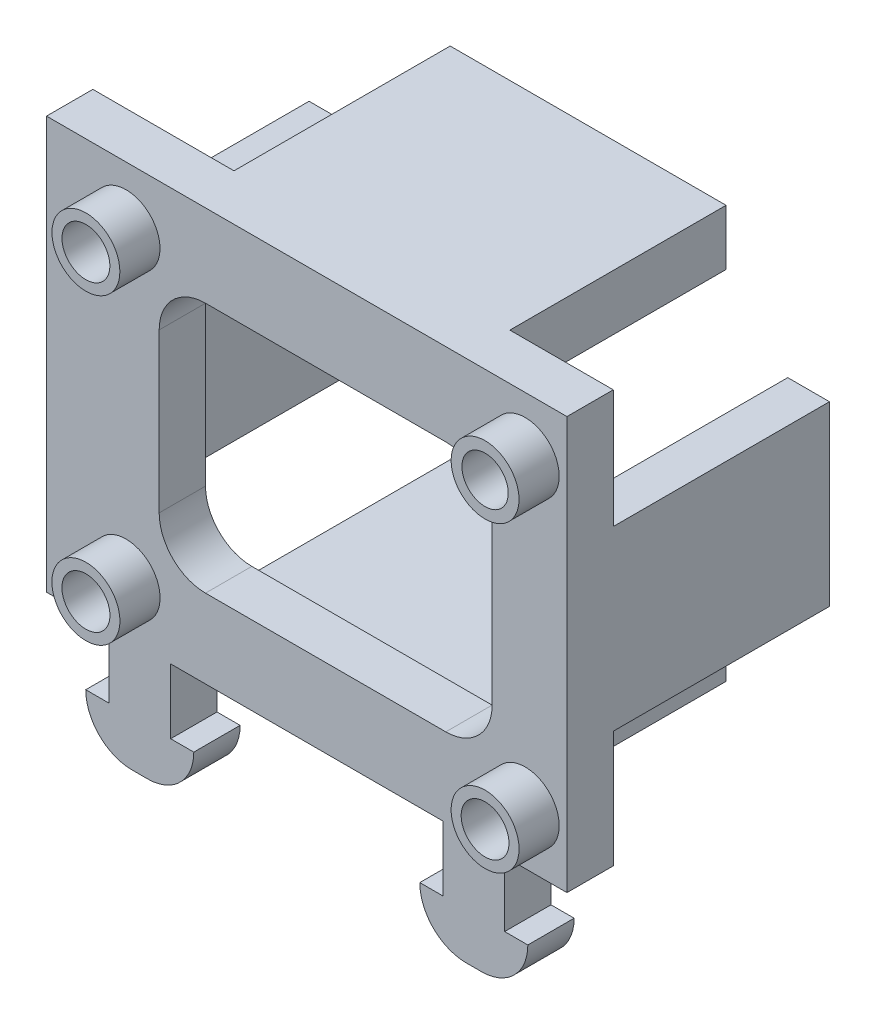
SolidWorks part; units mm, degrees
ref_plane "Спереди" through (0, 0, 0) normal (0, 0, 1) x (1, 0, 0)
ref_plane "Сверху" through (0, 0, 0) normal (0, 1, 0) x (1, 0, 0)
ref_plane "Справа" through (0, 0, 0) normal (1, 0, 0) x (0, 0, -1)
sketch "Эскиз2" plane through (0, 0, 0) normal (0, 0, 1) x (1, 0, 0)
  line L0 (33.7, 0) -> (30.9983, 0) construction
  line L1 (33.7, 26.7) -> (0, 26.7)
  line L2 (33.7, 26.7) -> (33.7, 0)
  line L3 (33.7, 0) -> (0, 0)
  line L4 (0, 26.7) -> (0, 0)
  line L5 (30.9983, 0) -> (30.9983, 3.4986) construction
  line L6 (30.9983, 3.4986) -> (33.7, 3.4986) construction
  line L7 (33.7, 26.7) -> (30.9983, 26.7) construction
  line L8 (30.9983, 26.7) -> (30.9983, 23.0985) construction
  line L9 (30.9983, 23.0985) -> (33.7, 23.0985) construction
  line L10 (0, 0) -> (5.1505, 0) construction
  line L11 (5.1505, 0) -> (5.1505, 3.3527) construction
  line L12 (5.1505, 3.3527) -> (0, 3.3527) construction
  line L13 (0, 26.7) -> (5.1505, 26.7) construction
  line L14 (5.1505, 26.7) -> (5.1505, 22.95) construction
  line L15 (5.1505, 22.95) -> (0, 22.95) construction
  line L16 (5.1505, 22.95) -> (30.9983, 3.4986) construction
  circle A0 centre (30.9983, 3.4986) radius 1.5002
  circle A1 centre (30.9983, 23.0985) radius 1.5
  circle A2 centre (5.1505, 3.3527) radius 1.5523
  circle A3 centre (5.1505, 22.95) radius 1.5465
  point P12 (30.9983, 21.5985)
  point P13 (30.9983, 4.9988)
  point P14 (30.9983, 1.9985)
  point P15 (30.9983, 24.5985)
  point P16 (32.4984, 3.4986)
  point P25 (5.1505, 21.4035)
  point P26 (5.1505, 24.4965)
  dimension "D1" = 26.7
  dimension "D2" = 33.7
extrude "Бобышка-Вытянуть1" add sketch "Эскиз2" along normal blind 2 and the other way blind 1
sketch "Эскиз4" plane through (0, 0, 2) normal (0, 0, 1) x (1, 0, 0)
  line L0 (5.1505, 22.95) -> (30.9983, 3.4986) construction
  line L2 (10.2935, 5.0944) -> (25.8553, 5.0944)
  line L3 (7.2935, 8.0944) -> (7.2935, 18.3542)
  line L4 (10.2935, 21.3542) -> (25.8553, 21.3542)
  line L5 (28.8553, 8.0944) -> (28.8553, 18.3542)
  line L6 (7.2935, 5.0944) -> (28.8553, 21.3542) construction
  line L7 (7.2935, 21.3542) -> (28.8553, 5.0944) construction
  arc A0 (25.8553, 5.0944) -> (28.8553, 8.0944) centre (25.8553, 8.0944) ccw
  arc A1 (10.2935, 5.0944) -> (7.2935, 8.0944) centre (10.2935, 8.0944) cw
  arc A2 (25.8553, 21.3542) -> (28.8553, 18.3542) centre (25.8553, 18.3542) cw
  arc A3 (7.2935, 18.3542) -> (10.2935, 21.3542) centre (10.2935, 18.3542) cw
  point P4 (18.0744, 13.2243)
  dimension "D3" = 3
  dimension "D4" = 3
  dimension "D5" = 3
  dimension "D6" = 3
  dimension "D1" = 16.2598
  dimension "D2" = 21.5618
extrude "Вырез-Вытянуть1" cut sketch "Эскиз4" against normal blind 3
sketch "Эскиз5" plane through (0, 0, 2) normal (0, 0, 1) x (1, 0, 0)
  circle A0 centre (5.1505, 22.95) radius 2.198
  circle A1 centre (30.9983, 23.0985) radius 2.1989
  circle A2 centre (30.9983, 3.4986) radius 2.2003
  circle A3 centre (5.1505, 3.3527) radius 2.2025
  dimension "D1" = 4.396
  dimension "D2" = 4.3978
  dimension "D3" = 4.4006
  dimension "D4" = 4.4049
extrude "Бобышка-Вытянуть2" add sketch "Эскиз5" along normal blind 2.6
sketch "Эскиз6" plane through (0, 0, 4.6) normal (0, 0, 1) x (1, 0, 0)
  circle A0 centre (5.1505, 22.95) radius 1.5512
  circle A1 centre (5.1505, 3.3527) radius 1.5547
  circle A2 centre (30.9983, 3.4986) radius 1.5482
  circle A3 centre (30.9983, 23.0985) radius 1.5
extrude "Вырез-Вытянуть2" cut sketch "Эскиз6" against normal blind 5
sketch "Эскиз10" plane through (0, 0, -1) normal (0, 0, -1) x (-1, 0, 0)
  line L0 (-30.9983, 3.4986) -> (-27.0046, 3.4986) construction
  line L1 (-27.0046, 3.4986) -> (-27.0046, 23.0985) construction
  line L2 (-5.1505, 3.3527) -> (-9.1386, 3.3527) construction
  line L3 (-9.1386, 3.3527) -> (-9.1386, 23.0985) construction
  line L4 (0, 0) -> (-33.7, 0) construction
  line L5 (-27.0046, 3.4986) -> (-9.1386, 3.4986)
  line L6 (-27.0046, 3.4986) -> (-27.0046, 0)
  line L7 (-27.0046, 0) -> (-9.1386, 0)
  line L8 (-9.1386, 3.4986) -> (-9.1386, 0)
  line L9 (-33.7, 26.7) -> (0, 26.7) construction
  line L10 (-27.0046, 23.0985) -> (-9.1386, 23.0985)
  line L11 (-27.0046, 23.0985) -> (-27.0046, 26.7)
  line L12 (-27.0046, 26.7) -> (-9.1386, 26.7)
  line L13 (-9.1386, 23.0985) -> (-9.1386, 26.7)
  line L14 (-30.9983, 3.4986) -> (-30.9983, 7.5529) construction
  line L15 (-30.9983, 23.0985) -> (-30.9983, 19.0325) construction
  line L16 (-33.7, 0) -> (-33.7, 26.7) construction
  line L17 (-30.9983, 7.5529) -> (-33.7, 7.5529)
  line L18 (-30.9983, 7.5529) -> (-30.9983, 19.0325)
  line L19 (-30.9983, 19.0325) -> (-33.7, 19.0325)
  line L20 (-33.7, 7.5529) -> (-33.7, 19.0325)
  line L21 (-5.1505, 7.5529) -> (-5.1505, 19.0325) construction
  line L22 (0, 26.7) -> (0, 0) construction
  line L23 (-5.1505, 7.5529) -> (0, 7.5529)
  line L24 (-5.1505, 7.5529) -> (-5.1505, 19.0325)
  line L25 (-5.1505, 19.0325) -> (0, 19.0325)
  line L26 (0, 7.5529) -> (0, 19.0325)
extrude "Бобышка-Вытянуть4" add sketch "Эскиз10" along normal blind 14
sketch "Эскиз11" plane through (0, 0, 0) normal (0, -1, 0) x (1, 0, 0)
  line L0 (0, 2) -> (4.0368, 2) construction
  line L1 (0, 2) -> (33.7, 2) construction
  line L2 (33.7, 2) -> (29.6665, 2) construction
  line L3 (4.0368, 2) -> (8.0379, 2)
  line L4 (4.0368, 2) -> (4.0368, -1.0003)
  line L5 (4.0368, -1.0003) -> (8.0379, -1.0003)
  line L6 (8.0379, 2) -> (8.0379, -1.0003)
  line L8 (29.6665, 2) -> (25.6707, 2)
  line L9 (29.6665, 2) -> (29.6665, -1)
  line L10 (29.6665, -1) -> (25.6707, -1)
  line L11 (25.6707, 2) -> (25.6707, -1)
extrude "Бобышка-Вытянуть5" add sketch "Эскиз11" along normal blind 4.2
sketch "Эскиз12" plane through (0, -4.2, 0) normal (0, -1, 0) x (1, 0, 0)
  line L0 (4.0368, 2) -> (8.0379, -1.0003) construction
  line L1 (25.6707, 2) -> (29.6665, -1) construction
  line L2 (2.5388, -1.0003) -> (9.5358, -1.0003)
  line L3 (2.5388, -1.0003) -> (2.5388, 2)
  line L4 (2.5388, 2) -> (9.5358, 2)
  line L5 (9.5358, -1.0003) -> (9.5358, 2)
  line L6 (2.5388, -1.0003) -> (9.5358, 2) construction
  line L7 (2.5388, 2) -> (9.5358, -1.0003) construction
  line L9 (24.1706, -1) -> (31.1666, -1)
  line L10 (24.1706, -1) -> (24.1706, 2)
  line L11 (24.1706, 2) -> (31.1666, 2)
  line L12 (31.1666, -1) -> (31.1666, 2)
  line L13 (24.1706, -1) -> (31.1666, 2) construction
  line L14 (24.1706, 2) -> (31.1666, -1) construction
  point P4 (6.0373, 0.4999)
  point P13 (27.6686, 0.5)
extrude "Бобышка-Вытянуть6" add sketch "Эскиз12" along normal blind 3
fillet "Скругление4" radius 3 1 edges at (2.5388, -7.2, 0.4999) type face fillet first side face at (2.5388, -5.7, 0.4999) second side face at (6.0373, -7.2, 0.4999)
fillet "Скругление5" radius 3 1 edges at (9.5358, -7.2, 0.4999) type face fillet first side face at (9.5358, -5.7, 0.4999) second side face at (7.5373, -7.2, 0.4999)
fillet "Скругление6" radius 3 1 edges at (31.1666, -7.2, 0.5) type face fillet first side face at (27.6686, -7.2, 0.5) second side face at (31.1666, -5.7, 0.5)
fillet "Скругление7" radius 3 1 edges at (24.1706, -7.2, 0.5) type face fillet first side face at (26.1686, -7.2, 0.5) second side face at (24.1706, -5.7, 0.5)
